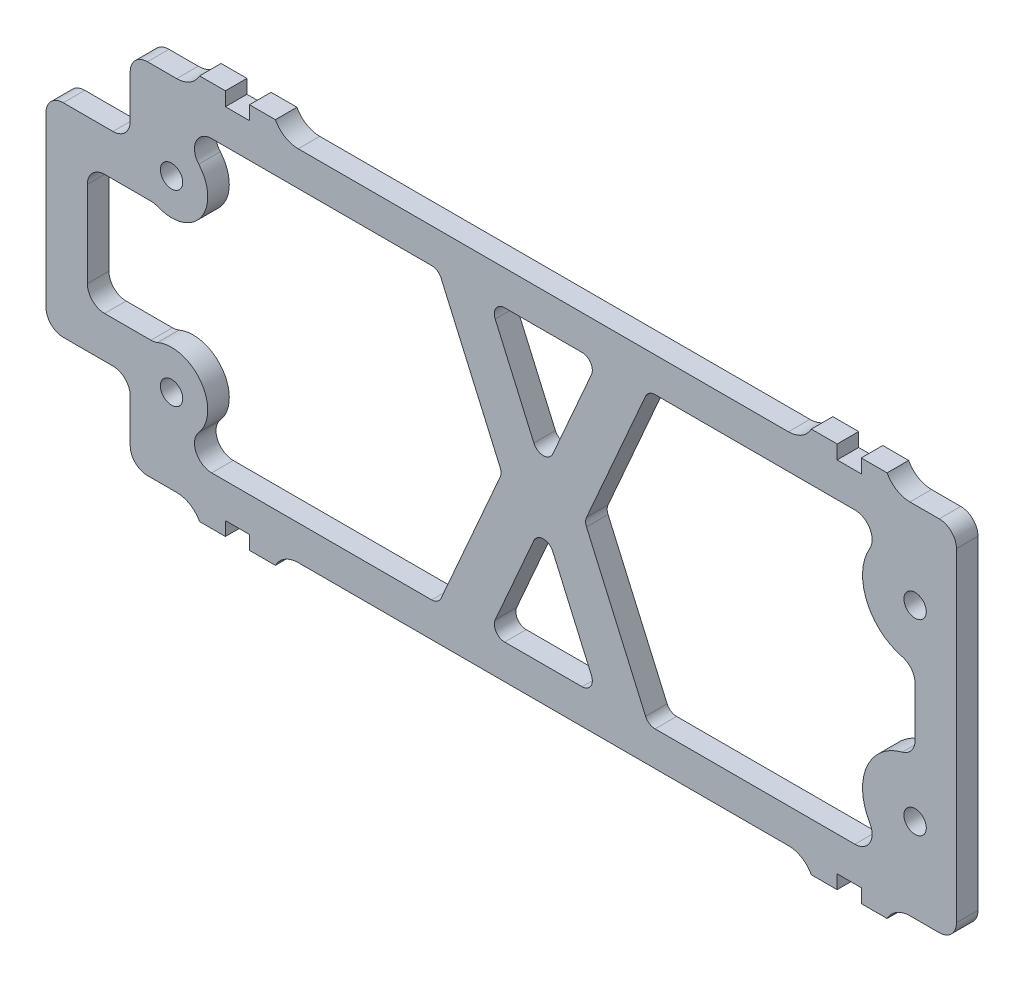
SolidWorks part; units mm, degrees
ref_plane "Front Plane" through (0, 0, 0) normal (0, 0, 1) x (1, 0, 0)
ref_plane "Top Plane" through (0, 0, 0) normal (0, 1, 0) x (1, 0, 0)
ref_plane "Right Plane" through (0, 0, 0) normal (1, 0, 0) x (0, 0, -1)
sketch "Sketch1" plane through (0, 0, 0) normal (0, 0, 1) x (1, 0, 0)
  line L0 (-7.752, 24.708) -> (-12.8635, 24.708)
  line L1 (0, 11.5) -> (-76.793, 11.5) construction
  line L2 (0, 23) -> (0, 0) construction
  line L3 (-68.648, 15.9388) -> (-71.8058, 15.9388)
  line L4 (-62.6419, 22.168) -> (-45.9346, 22.168)
  line L5 (-68.648, 15.9388) -> (-67.1213, 15.9388)
  line L6 (-10.8, 18.3) -> (-65.6, 18.3) construction
  line L7 (-38.2, 18.3) -> (-38.2, 37.5873) construction
  line L8 (-10.8, 13.3163) -> (-10.8, 9.6837)
  line L9 (-7.752, 24.708) -> (-7.752, 11.5)
  line L10 (-71.8058, 15.9388) -> (-71.8058, 11.5)
  line L11 (-69.9008, 14.0338) -> (-69.9008, 9.0808) construction
  line L12 (-42.2171, 22.168) -> (-38.2, 13.024)
  line L13 (-68.648, 24.708) -> (-68.648, 18.9868)
  line L14 (-68.648, 24.708) -> (-63.5365, 24.708)
  line L16 (-34.1829, 22.168) -> (-38.2, 13.024)
  line L17 (-7.752, -1.708) -> (-7.752, 11.5)
  line L18 (-7.752, -1.708) -> (-12.8635, -1.708)
  line L19 (-39.3137, 15.5591) -> (-37.0863, 15.5591) construction
  line L20 (-45.9346, 22.168) -> (-41.248, 11.5)
  line L21 (-30.4654, 22.168) -> (-35.152, 11.5)
  line L22 (-68.648, -1.708) -> (-63.5365, -1.708)
  line L23 (-68.648, -1.708) -> (-68.648, 4.0132)
  line L24 (-42.2171, 22.168) -> (-34.1829, 22.168)
  line L25 (-64.9478, 14.0338) -> (-69.9008, 14.0338) construction
  line L26 (-68.648, 18.9868) -> (-74.8538, 18.9868)
  line L27 (-74.8538, 18.9868) -> (-74.8538, 11.5)
  line L28 (-30.4654, 22.168) -> (-15.2385, 22.168)
  line L29 (-68.648, 4.0132) -> (-74.8538, 4.0132)
  line L30 (-74.8538, 4.0132) -> (-74.8538, 11.5)
  line L31 (-30.4654, 0.832) -> (-15.2385, 0.832)
  line L32 (-30.4654, 0.832) -> (-35.152, 11.5)
  line L33 (-34.1829, 0.832) -> (-38.2, 9.976)
  line L34 (-42.2171, 0.832) -> (-34.1829, 0.832)
  line L35 (-42.2171, 0.832) -> (-38.2, 9.976)
  line L36 (-45.9346, 0.832) -> (-41.248, 11.5)
  line L37 (-62.6419, 0.832) -> (-45.9346, 0.832)
  line L38 (-68.648, 7.0612) -> (-67.1213, 7.0612)
  line L39 (-68.648, 7.0612) -> (-71.8058, 7.0612)
  line L40 (-30.734, 17.7676) -> (-30.734, 8.014)
  line L41 (-30.734, 8.014) -> (-25.2476, 8.014)
  line L42 (-25.2476, 8.014) -> (-25.2476, 17.7676)
  line L43 (-25.2476, 17.7676) -> (-30.734, 17.7676)
  line L44 (-30.734, 17.7676) -> (-30.734, 8.014) construction
  line L45 (-30.734, 8.014) -> (-25.2476, 8.014) construction
  line L46 (-25.2476, 8.014) -> (-25.2476, 17.7676) construction
  line L47 (-25.2476, 17.7676) -> (-30.734, 17.7676) construction
  line L48 (-71.8058, 7.0612) -> (-71.8058, 11.5)
  line L49 (-38.2, 18.3) -> (-38.2, -6.1222) construction
  line L50 (-14.7685, 24.708) -> (-14.7685, 25.724)
  line L51 (-14.7685, 25.724) -> (-12.8635, 25.724)
  line L52 (-12.8635, 25.724) -> (-12.8635, 24.708)
  line L53 (-14.7685, 24.708) -> (-16.5465, 24.708)
  line L54 (-57.9485, 24.708) -> (-57.9485, 25.724)
  line L55 (-57.9485, 25.724) -> (-59.8535, 25.724)
  line L56 (-59.8535, 25.724) -> (-59.8535, 24.708)
  line L57 (-61.6315, 24.708) -> (-59.8535, 24.708)
  line L58 (-63.5365, -2.724) -> (-63.5365, -1.708)
  line L59 (-61.6315, -2.724) -> (-63.5365, -2.724)
  line L60 (-61.6315, -1.708) -> (-61.6315, -2.724)
  line L61 (-14.7685, -1.708) -> (-14.7685, -2.724)
  line L62 (-14.7685, -2.724) -> (-12.8635, -2.724)
  line L63 (-12.8635, -2.724) -> (-12.8635, -1.708)
  line L64 (-14.7685, -1.708) -> (-16.5465, -1.708)
  line L65 (-61.6315, -1.708) -> (-59.8535, -1.708)
  line L66 (-18.4515, 24.708) -> (-18.4515, 25.724)
  line L67 (-18.4515, 25.724) -> (-16.5465, 25.724)
  line L68 (-16.5465, 25.724) -> (-16.5465, 24.708)
  line L69 (-18.4515, 24.708) -> (-38.2, 24.708)
  line L70 (-61.6315, 24.708) -> (-61.6315, 25.724)
  line L71 (-61.6315, 25.724) -> (-63.5365, 25.724)
  line L72 (-63.5365, 25.724) -> (-63.5365, 24.708)
  line L73 (-59.8535, -2.724) -> (-59.8535, -1.708)
  line L74 (-57.9485, -2.724) -> (-59.8535, -2.724)
  line L75 (-57.9485, -1.708) -> (-57.9485, -2.724)
  line L76 (-18.4515, -1.708) -> (-18.4515, -2.724)
  line L77 (-18.4515, -2.724) -> (-16.5465, -2.724)
  line L78 (-16.5465, -2.724) -> (-16.5465, -1.708)
  line L79 (-57.9485, 24.708) -> (-38.2, 24.708)
  line L80 (-57.9485, -1.708) -> (-38.2, -1.708)
  line L81 (-18.4515, -1.708) -> (-38.2, -1.708)
  arc A0 (-14.1425, 20.2565) -> (-11.7564, 14.5469) centre (-10.8, 18.3) ccw
  circle A1 centre (-10.8, 18.3) radius 0.825 construction
  arc A2 (-14.1425, 20.2565) -> (-15.2385, 22.168) centre (-15.2385, 20.898) ccw
  circle A3 centre (-10.8, 18.3) radius 0.825
  circle A4 centre (-10.8, 18.3) radius 3.873 construction
  arc A5 (-11.7564, 14.5469) -> (-10.8, 13.3163) centre (-12.07, 13.3163) cw
  arc A6 (-63.5961, 20.0599) -> (-62.6419, 22.168) centre (-62.6419, 20.898) cw
  arc A7 (-11.7564, 8.4531) -> (-10.8, 9.6837) centre (-12.07, 9.6837) ccw
  circle A8 centre (-65.6, 18.3) radius 2.667
  arc A9 (-66.6306, 15.8402) -> (-63.5961, 20.0599) centre (-65.6, 18.3) ccw
  arc A10 (-67.1213, 15.9388) -> (-66.6306, 15.8402) centre (-67.1213, 14.6688) cw
  arc A11 (-14.1425, 2.7436) -> (-11.7564, 8.4531) centre (-10.8, 4.7) cw
  arc A12 (-14.1425, 2.7436) -> (-15.2385, 0.832) centre (-15.2385, 2.102) cw
  arc A13 (-63.5961, 2.9401) -> (-62.6419, 0.832) centre (-62.6419, 2.102) ccw
  arc A14 (-66.6306, 7.1599) -> (-63.5961, 2.9401) centre (-65.6, 4.7) cw
  arc A15 (-67.1213, 7.0612) -> (-66.6306, 7.1599) centre (-67.1213, 8.3312) ccw
  circle A20 centre (-10.8, 4.5) radius 0.825 construction
  circle A21 centre (-10.8, 4.5) radius 0.825
  circle A22 centre (-65.6, 18.3) radius 0.825 construction
  circle A23 centre (-65.6, 18.3) radius 0.825
  circle A24 centre (-65.6, 4.5) radius 0.825 construction
  circle A25 centre (-65.6, 4.5) radius 0.825
  point P18 (-6.927, 18.3)
  point P35 (-38.2, 11.5)
  point P51 (-38.2, 15.5591)
  point P57 (-10.8, 11.5)
  dimension "D2" = 2.54
  dimension "D3" = 6.096
  dimension "D4" = 1.905
  dimension "D16" = 1.27
  dimension "D5" = 1.27
  dimension "D10" = 1.27
  dimension "D18" = 1.27
  dimension "D6" = 3.048
  dimension "D7" = 13.208
  dimension "D8" = 1.905
  dimension "D9" = 3.048
  dimension "D11" = 1.524
  dimension "D12" = 3.048
  dimension "D15" = 1.524
  dimension "D19" = 1.524
  dimension "D20" = 1.905
  dimension "D21" = 43.307
  dimension "D22" = 1.016
  dimension "D23" = 1.778
  dimension "D13" = 3.048
  dimension "D14" = 0
  dimension "D17" = 1.905
extrude "Boss-Extrude1" add sketch "Sketch1" along normal blind 1.5875
fillet "Fillet4" radius 0.762 12 edges at (-30.4654, 22.168, 0.7937) (-45.9346, 22.168, 0.7937) (-41.248, 11.5, 0.7937) (-35.152, 11.5, 0.7937) (-30.4654, 0.832, 0.7937) (-45.9346, 0.832, 0.7937) (-42.2171, 0.832, 0.7937) (-34.1829, 0.832, 0.7937) (-38.2, 9.976, 0.7937) (-38.2, 13.024, 0.7937) (-34.1829, 22.168, 0.7937) (-42.2171, 22.168, 0.7937)
fillet "Fillet5" radius 1.27 10 edges at (-7.752, 24.708, 0.7937) (-68.648, -1.708, 0.7937) (-68.648, 4.0132, 0.7937) (-74.8538, 4.0132, 0.7937) (-74.8538, 18.9868, 0.7937) (-68.648, 18.9868, 0.7937) (-71.8058, 7.0612, 0.7937) (-71.8058, 15.9388, 0.7937) (-68.648, 24.708, 0.7937) (-7.752, -1.708, 0.7937)
fillet "Fillet6" radius 1.905 8 edges at (-18.4515, -1.708, 0.7937) (-12.8635, -1.708, 0.7937) (-18.4515, 24.708, 0.7937) (-12.8635, 24.708, 0.7937) (-57.9485, 24.708, 0.7937) (-63.5365, 24.708, 0.7937) (-63.5365, -1.708, 0.7937) (-57.9485, -1.708, 0.7937)
